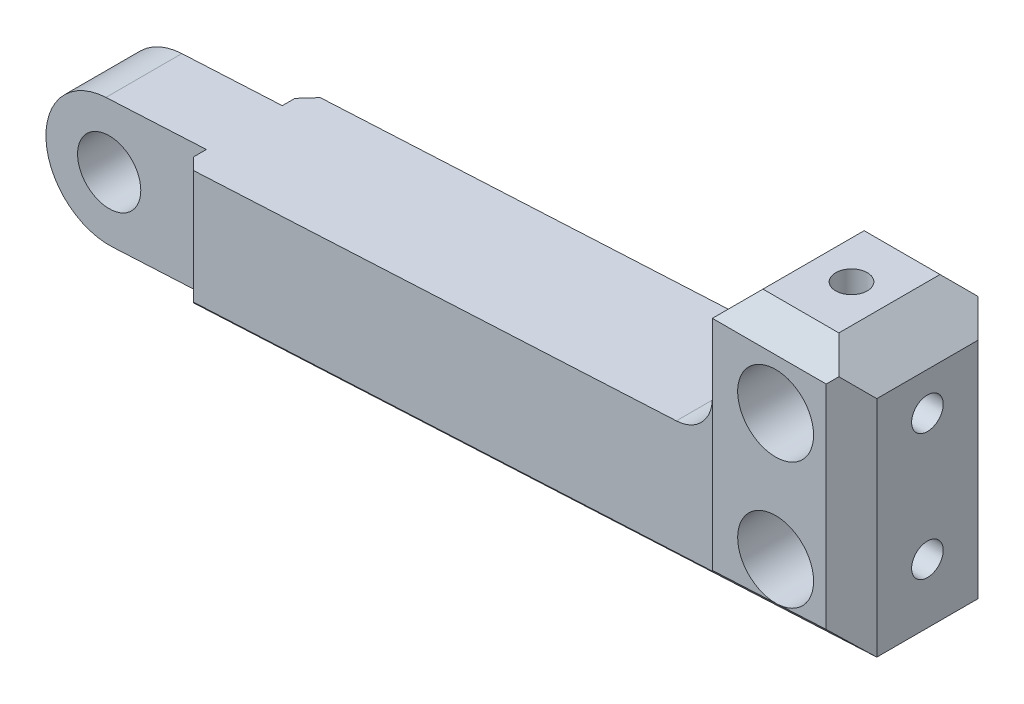
SolidWorks part; units mm, degrees
material "6061"
ref_plane "Front" through (0, 0, 0) normal (0, 0, 1) x (1, 0, 0)
ref_plane "Top" through (0, 0, 0) normal (0, 1, 0) x (1, 0, 0)
ref_plane "Right" through (0, 0, 0) normal (1, 0, 0) x (0, 0, -1)
sketch "Sketch1" plane through (0, 0, 0) normal (0, 0, 1) x (1, 0, 0)
  line L0 (0, 20.7) -> (0, 0)
  line L1 (0, 0) -> (-61.4313, -3.1335)
  line L3 (-61.9407, 6.8535) -> (-12, 9.4009)
  line L4 (-12, 9.4009) -> (-12, 20.7)
  line L5 (-12, 20.7) -> (0, 20.7)
  arc A0 (-61.9407, 6.8535) -> (-61.4313, -3.1335) centre (-61.686, 1.86) ccw
  dimension "D1" = 12
  dimension "D2" = 10
  dimension "D3" = 20.7
  dimension "D4" = 92.92
  dimension "D5" = 61.686
extrude "Boss-Extrude1" add sketch "Sketch1" along normal mid plane 12
sketch "Sketch2" plane through (0, 0, 0) normal (0, 1, 0) x (1, 0, 0)
  line L0 (-66.686, 6) -> (-66.686, -6) construction
  line L1 (-66.686, 6) -> (-54, 6)
  line L2 (-66.686, 6) -> (-66.686, 3)
  line L3 (-66.686, 3) -> (-54, 3)
  line L4 (-54, 6) -> (-54, 3)
  line L5 (-66.686, -3) -> (-54, -3)
  line L6 (-66.686, -3) -> (-66.686, -6)
  line L7 (-66.686, -6) -> (-54, -6)
  line L8 (-54, -3) -> (-54, -6)
  line L9 (-61.4313, 6) -> (-66.686, 6) construction
  line L10 (-70.3586, 0) -> (3.1401, 0) construction
  line L11 (-12, -6) -> (-61.9407, -6) construction
  line L12 (0, -6) -> (0, 6) construction
  dimension "D1" = 6
  dimension "D2" = 54
extrude "Cut-Extrude1" cut sketch "Sketch2" against normal through all and the other way through all
sketch "Sketch11" plane through (0, 0, 0) normal (0, 1, 0) x (1, 0, 0)
  line L0 (-12, -6) -> (-12, 6) construction
  line L1 (-54, 6) -> (-12, 6)
  line L2 (-54, 6) -> (-54, 5)
  line L3 (-54, 5) -> (-12, 5)
  line L4 (-12, 6) -> (-12, 5)
  line L5 (-68.6328, 0) -> (1.3441, 0) construction
  line L6 (-12, -5) -> (-54, -5)
  line L7 (-12, -5) -> (-12, -6)
  line L8 (-12, -6) -> (-54, -6)
  line L9 (-54, -5) -> (-54, -6)
  dimension "D1" = 10
extrude "Cut-Extrude2" cut sketch "Sketch11" against normal through all and the other way through all
sketch "Sketch3" plane through (0, 0, 6) normal (0, 0, 1) x (1, 0, 0)
  line L0 (0, 0) -> (0, 20.7) construction
  circle A0 centre (-6, 4.7) radius 3
  circle A1 centre (-6, 14.7) radius 3
  dimension "D2" = 6
  dimension "D1" = 6
  dimension "D3" = 4.7
  dimension "D4" = 10
extrude "Cut-Extrude3" cut sketch "Sketch3" against normal through all
sketch "Sketch4" plane through (0, 0, 3) normal (0, 0, 1) x (1, 0, 0)
  circle A0 centre (-61.686, 1.86) radius 2.5
  dimension "D1" = 5
extrude "Cut-Extrude4" cut sketch "Sketch4" against normal through all
hole_wizard "M3x0.5 Tapped Hole1" positions "Sketch8" profile "Sketch7" tap size "M3x0.5" standard "JIS" end condition up to next
sketch "Sketch8" plane through (0, 0, 0) normal (1, 0, 0) x (0, 0, -1)
  point P0 (0, 14.7)
  point P1 (0, 4.7)
sketch "Sketch7" plane through (0, 14.7, 0) normal (0, 1, 0) x (0, 0, -1)
  line L0 (0, 0) -> (0, 3)
  line L1 (0, 3) -> (1.25, 3)
  line L2 (1.25, 3) -> (1.25, 0)
  line L5 (1.25, 0) -> (0, 0)
  line L11 (0, -6.35) -> (0, 107.95) construction
  dimension "Thru Tap Drill Dia." = 2.5
  dimension "Thru Tap Drill Depth" = 3
cosmetic thread "Hole Thread1" parameters "D2"=3
cosmetic thread "Hole Thread2" parameters "D2"=3
hole_wizard "M3x0.5 Tapped Hole2" positions "Sketch10" profile "Sketch9" tap size "M3x0.5" standard "JIS" end condition up to next
sketch "Sketch10" plane through (0, 20.7, 0) normal (0, 1, 0) x (-1, 0, 0)
  point P0 (6, 0)
sketch "Sketch9" plane through (-6, 20.7, 0) normal (1, 0, 0) x (0, 0, 1)
  line L0 (0, 0) -> (0, 3)
  line L1 (0, 3) -> (1.25, 3)
  line L2 (1.25, 3) -> (1.25, 0)
  line L5 (1.25, 0) -> (0, 0)
  line L11 (0, -6.35) -> (0, 107.95) construction
  dimension "Thru Tap Drill Dia." = 2.5
  dimension "Thru Tap Drill Depth" = 3
cosmetic thread "Hole Thread3" parameters "D2"=3
fillet "Fillet1" radius 3 1 edges at (-12, 9.4009, 0)
chamfer "Chamfer1" distance 3 angle 45 2 edges at (-12, 20.7, 0) (0, 20.7, 0)
chamfer "Chamfer2" distance 2 angle 45 6 edges at (-6, -0.306, -6) (0, 8.85, -6) (-6, -0.306, 6) (0, 8.85, 6) (-6, 20.7, 6) (-6, 20.7, -6)
chamfer "Chamfer3" distance 1 angle 45 4 edges at (-12, 9.5453, -6) (-12, 9.5453, 6) (-54, 2.7527, -5) (-54, 2.7527, 5)
